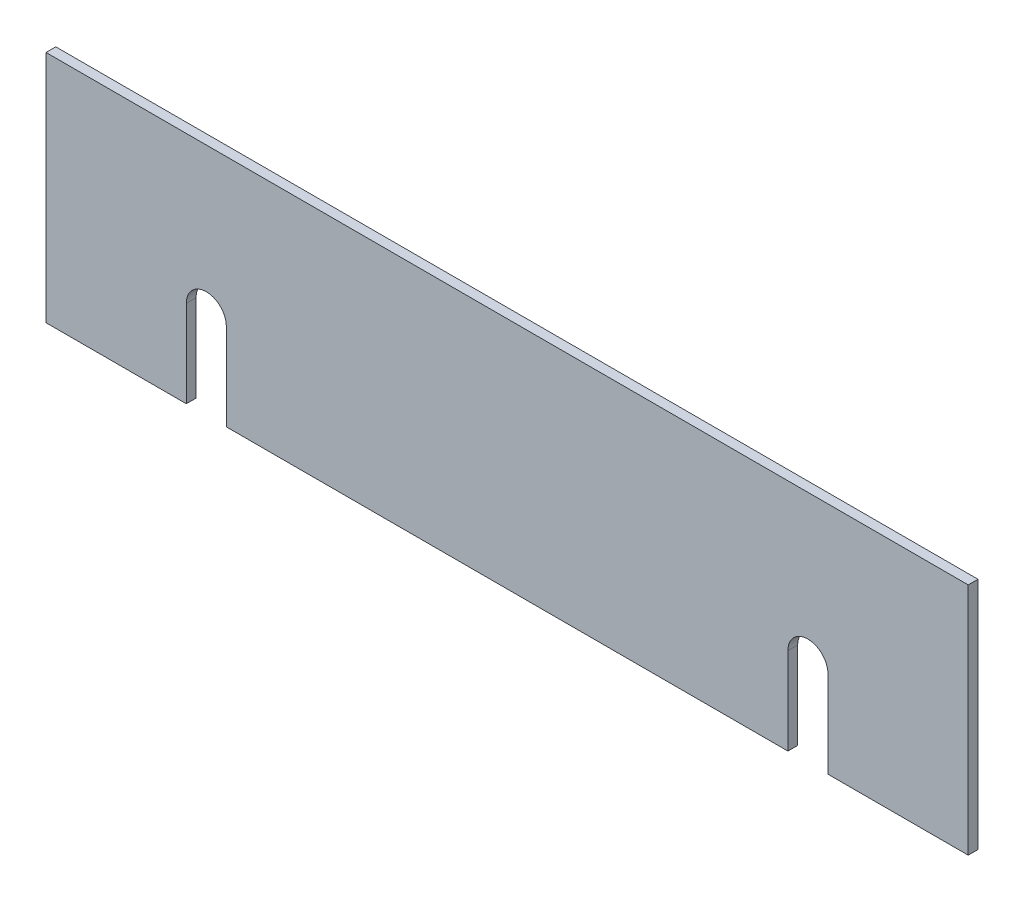
SolidWorks part; units mm, degrees
material "ABS"
ref_plane "X-Y Datum" through (0, 0, 0) normal (0, 0, 1) x (1, 0, 0)
ref_plane "X-Z Datum" through (0, 0, 0) normal (0, 1, 0) x (1, 0, 0)
ref_plane "Y-Z Datum" through (0, 0, 0) normal (1, 0, 0) x (0, 0, -1)
sketch "Sketch1" plane through (0, 0, 0) normal (0, 0, 1) x (1, 0, 0)
  line L1 (-149.85, 38.0375) -> (149.85, 38.0375)
  line L2 (-149.85, 38.0375) -> (-149.85, -38.0375)
  line L3 (-149.85, -38.0375) -> (149.85, -38.0375)
  line L4 (149.85, 38.0375) -> (149.85, -38.0375)
  line L5 (-149.85, 38.0375) -> (149.85, -38.0375) construction
  line L6 (-149.85, -38.0375) -> (149.85, 38.0375) construction
  point P0 (0, 0)
  dimension "D1" = 76.075
  dimension "D2" = 299.7
extrude "Boss-Extrude1" add sketch "Sketch1" along normal blind 3.175
sketch "Sketch3" plane through (0, 0, 0) normal (0, 0, -1) x (-1, 0, 0)
  line L0 (104.25, -9.7625) -> (104.25, -38.0375)
  line L1 (149.85, -38.0375) -> (-149.85, -38.0375) construction
  line L2 (91.25, -9.7625) -> (91.25, -38.0375)
  line L3 (149.85, -38.0375) -> (-149.85, -38.0375)
  line L4 (-104.25, -9.7625) -> (-104.25, -38.0375)
  line L5 (-91.25, -9.7625) -> (-91.25, -38.0375)
  circle A0 centre (97.75, -9.7625) radius 5.75 construction
  circle A1 centre (-97.75, -9.7625) radius 5.75 construction
  circle A2 centre (97.75, -9.7625) radius 5.75 construction
  circle A3 centre (-97.75, -9.7625) radius 5.75 construction
  circle A4 centre (97.75, -9.7625) radius 6.5
  circle A5 centre (-97.75, -9.7625) radius 6.5
  line M2 (-149.85, -38.0375) -> (149.85, -38.0375)
  dimension "D1" = 13
extrude "Cut-Extrude1" cut sketch "Sketch3" against normal through all contours A5 A3 | A3 | A5 L4 L3 L5 | A2 | A4 A2 | A4 L2 L0 M2 region at (97.75, -26.4071, 0) region at (-97.75, -9.7625, 0) region at (-97.75, -26.4071, 0) region at (97.75, -9.7625, 0)
